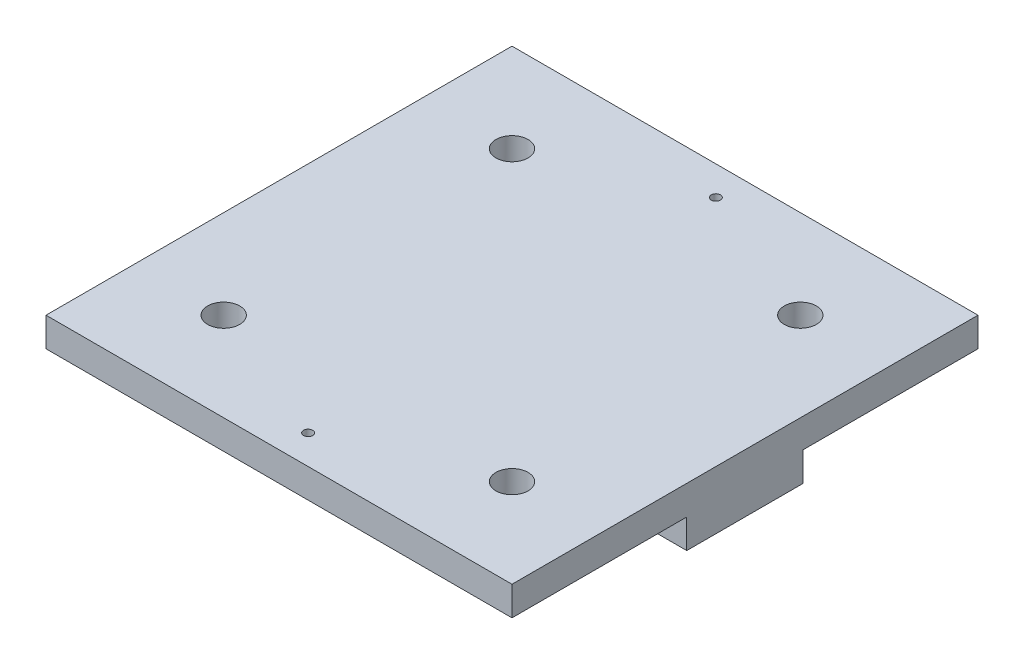
SolidWorks part; units mm, degrees
ref_plane "Front Plane" through (0, 0, 0) normal (0, 0, 1) x (1, 0, 0)
ref_plane "Top Plane" through (0, 0, 0) normal (0, 1, 0) x (1, 0, 0)
ref_plane "Right Plane" through (0, 0, 0) normal (1, 0, 0) x (0, 0, -1)
sketch "Sketch1" plane through (0, 0, 0) normal (0, 1, 0) x (1, 0, 0)
  line L1 (-50.8, -50.8) -> (50.8, -50.8)
  line L2 (-50.8, -50.8) -> (-50.8, 50.8)
  line L3 (-50.8, 50.8) -> (50.8, 50.8)
  line L4 (50.8, -50.8) -> (50.8, 50.8)
  line L5 (-50.8, -50.8) -> (50.8, 50.8) construction
  line L6 (-50.8, 50.8) -> (50.8, -50.8) construction
  point P0 (0, 0)
  dimension "D1" = 101.6
  dimension "D2" = 101.6
extrude "Mounting surface" add sketch "Sketch1" along normal blind 6.35
sketch "Sketch7" plane through (0, 0, 0) normal (0, -1, 0) x (-1, 0, 0)
  line L0 (-50.8, 0) -> (50.8, 0) construction
  line L1 (-50.8, -50.8) -> (-50.8, 50.8) construction
  line L2 (50.8, 50.8) -> (50.8, -50.8) construction
  line L4 (50.8, 12.7) -> (-50.8, 12.7)
  line L5 (50.8, 12.7) -> (50.8, -12.7)
  line L6 (50.8, -12.7) -> (-50.8, -12.7)
  line L7 (-50.8, 12.7) -> (-50.8, -12.7)
  line L8 (50.8, 12.7) -> (-50.8, -12.7) construction
  line L9 (50.8, -12.7) -> (-50.8, 12.7) construction
  point P6 (0, 0)
  dimension "D1" = 25.4
extrude "grab flange" add sketch "Sketch7" along normal blind 6.35
sketch "mounting location" plane through (0, 6.35, 0) normal (0, 1, 0) x (1, 0, 0)
  line L0 (0, 0) -> (50.8, 0) construction
  line L1 (50.8, -50.8) -> (50.8, 50.8) construction
  line L2 (0, 0) -> (31.4309, 31.4309) construction
  circle A0 centre (0, 0) radius 44.45 construction
  point P3 (31.4309, 31.4309)
  point P4 (0, 44.45)
  point P9 (0, -44.45)
  point P11 (31.4309, -31.4309)
  point P12 (-31.4309, -31.4309)
  point P13 (-31.4309, 31.4309)
  point P14 (0, 0)
  dimension "D1" = 88.9
  dimension "D2" = 45
  dimension "D3" = 4
hole_wizard "M8x1.0 Tapped Hole2" positions "Sketch9" profile "Sketch10" tap size "M8x1.0" standard "ANSI Metric" end condition through all
sketch "Sketch9" plane through (0, 6.35, 0) normal (0, 1, 0) x (1, 0, 0)
  point P0 (31.4309, 31.4309)
  point P3 (-31.4309, 31.4309)
  point P6 (-31.4309, -31.4309)
  point P9 (31.4309, -31.4309)
sketch "Sketch10" plane through (31.4309, 6.35, -31.4309) normal (1, 0, 0) x (0, 0, 1)
  line L0 (0, 0) -> (0, 12.7)
  line L1 (0, 12.7) -> (3.5, 12.7)
  line L2 (3.5, 12.7) -> (3.5, 0)
  line L5 (3.5, 0) -> (0, 0)
  line L11 (0, -6.35) -> (0, 107.95) construction
  dimension "Thru Tap Drill Dia." = 7
  dimension "Thru Tap Drill Depth" = 12.7
cosmetic thread "Hole Thread5" parameters "D2"=8
cosmetic thread "Hole Thread6" parameters "D2"=8
cosmetic thread "Hole Thread7" parameters "D2"=8
cosmetic thread "Hole Thread8" parameters "D2"=8
hole_wizard "Ø2.0mm Press Dowel Hole2" positions "Sketch11" profile "Sketch12" hole size "Ø2.0" standard "ANSI Metric" end condition through all
sketch "Sketch11" plane through (0, 6.35, 0) normal (0, 1, 0) x (1, 0, 0)
  point P0 (0, 44.45)
  point P3 (0, -44.45)
sketch "Sketch12" plane through (0, 6.35, -44.45) normal (1, 0, 0) x (0, 0, 1)
  line L0 (0, 0) -> (0, 12.7)
  line L1 (0, 12.7) -> (1, 12.7)
  line L2 (1, 12.7) -> (1, 0)
  line L5 (1, 0) -> (0, 0)
  line L11 (0, -6.35) -> (0, 107.95) construction
  dimension "Thru Hole Dia." = 2
  dimension "Thru Hole Depth" = 12.7
